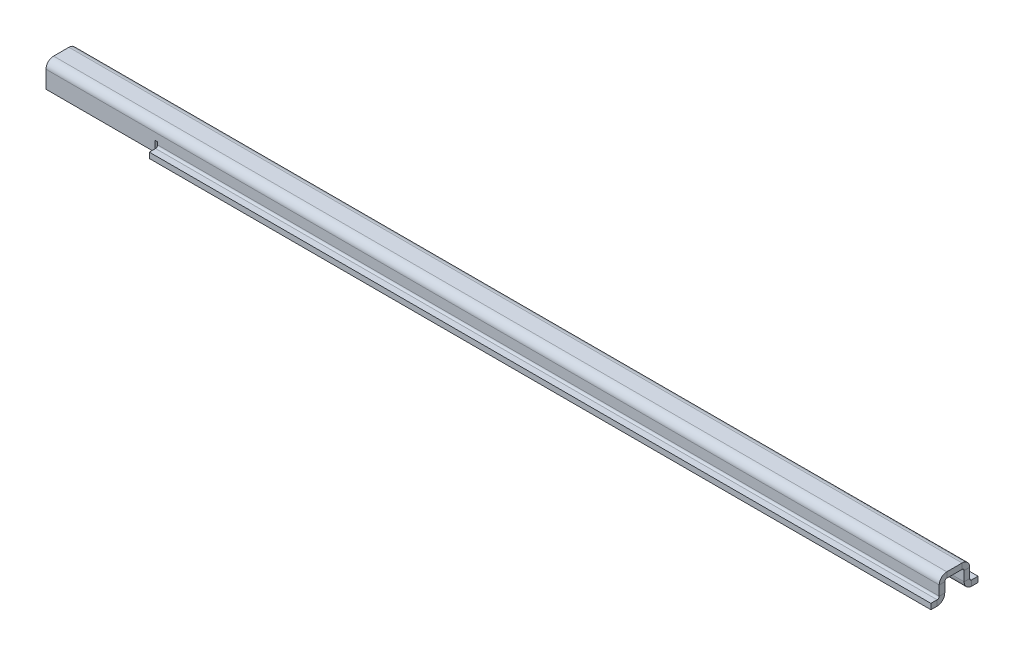
SolidWorks part; units mm, degrees
note: The reader was unsure of these and kept them because the rebuilt part matched: flange length of "Edge-Flange1", "Edge-Flange3".
material "ASTM A36 Steel"
ref_plane "Front Plane" through (0, 0, 0) normal (0, 0, 1) x (1, 0, 0)
ref_plane "Top Plane" through (0, 0, 0) normal (0, 1, 0) x (1, 0, 0)
ref_plane "Right Plane" through (0, 0, 0) normal (1, 0, 0) x (0, 0, -1)
sketch "Sketch2" plane through (0, 0, 0) normal (0, 1, 0) x (1, 0, 0)
  line L1 (-161.2, 5.5) -> (161.2, 5.5)
  line L2 (-161.2, 5.5) -> (-161.2, -5.5)
  line L3 (-161.2, -5.5) -> (161.2, -5.5)
  line L4 (161.2, 5.5) -> (161.2, -5.5)
  line L5 (-161.2, 5.5) -> (161.2, -5.5) construction
  line L6 (-161.2, -5.5) -> (161.2, 5.5) construction
  point P0 (0, 0)
  dimension "D1" = 322.4
  dimension "D2" = 11
base flange "Base-Flange1" sketch "Sketch2" thickness 2 reverse thickness direction no parameters "D1"=0.7366
edge flange "Edge-Flange1" sketch "Sketch11" flange profiles "Sketch11", "Sketch12" flange angle 90 flange length 9 flange position material inside bend radius 0.7366 thickness 2 relief rectangular parameters "D6"=10, "D8"=1
sketch "Sketch11" plane through (0, -2, 5.5) normal (0, 0, 1) x (-1, 0, 0)
  line L0 (161.2, 0) -> (-161.2, 0) construction
  line L1 (161.2, 0) -> (-161.2, 0)
  line L2 (-161.2, 0) -> (-161.2, 7)
  line L3 (-161.2, 7) -> (161.2, 7)
  line L4 (161.2, 7) -> (161.2, 0)
sketch "Sketch12" plane through (0, -2, -5.5) normal (0, 0, -1) x (1, 0, 0)
  line L0 (161.2, 0) -> (-161.2, 0) construction
  line L1 (161.2, 0) -> (-161.2, 0)
  line L2 (-161.2, 0) -> (-161.2, 7)
  line L3 (-161.2, 7) -> (161.2, 7)
  line L4 (161.2, 7) -> (161.2, 0)
bend "EdgeBend1" bend radius 0.7366 bend angle 90 parameters "D5"=1
bend "EdgeBend2" bend radius 0.7366 bend angle 90 parameters "D5"=2
sketch "Sketch15" plane through (0, 0, -5.5) normal (0, 0, -1) x (-1, 0, 0)
  line L0 (-161.2, -9) -> (161.2, -9) construction
  line L1 (-140, -9) -> (-70, -9)
  line L2 (-140, -9) -> (-140, -15)
  line L3 (-140, -15) -> (-70, -15)
  line L4 (-70, -9) -> (-70, -15)
  line L5 (0, 46.1369) -> (0, -97.287) construction
  line L6 (-35, -9) -> (35, -9)
  line L7 (-35, -9) -> (-35, -15)
  line L8 (-35, -15) -> (35, -15)
  line L9 (35, -9) -> (35, -15)
  line L10 (70, -9) -> (140, -9)
  line L11 (70, -9) -> (70, -15)
  line L12 (70, -15) -> (140, -15)
  line L13 (140, -9) -> (140, -15)
  dimension "D1" = 70
  dimension "D2" = 35
  dimension "D3" = 35
  dimension "D4" = 6
edge flange "Edge-Flange3" sketch "Sketch31" flange profiles "Sketch31", "Sketch32" flange angle 90 flange length 5 flange position material inside bend radius 0.7366 thickness 2 relief rectangular parameters "D6"=10, "D8"=1
sketch "Sketch31" plane through (0, -9, 5.5) normal (0, -1, 0) x (1, 0, 0)
  line L0 (-161.2, 0) -> (-161.2, -2) construction
  line L2 (-120.9, 0) -> (-120.9, 3)
  line L3 (-120.9, 3) -> (161.2, 3)
  line L4 (161.2, 3) -> (161.2, 0)
  line L11 (-161.2, 0) -> (161.2, 0) construction
  line L12 (-120.9, 0) -> (161.2, 0)
  dimension "D1" = 40.3
sketch "Sketch32" plane through (0, -9, -5.5) normal (0, -1, 0) x (-1, 0, 0)
  line L0 (161.2, 0) -> (161.2, -2) construction
  line L2 (120.9, 0) -> (120.9, 3)
  line L3 (120.9, 3) -> (-161.2, 3)
  line L4 (-161.2, 3) -> (-161.2, 0)
  line L5 (-161.2, 0) -> (161.2, 0) construction
  line L6 (-161.2, 0) -> (120.9, 0)
  dimension "D1" = 40.3
bend "EdgeBend5" bend radius 0.7366 bend angle 90 parameters "D5"=3
bend "EdgeBend6" bend radius 0.7366 bend angle 90 parameters "D5"=4
sketch "Bend-Lines1" [suppressed] plane through (0, 0, 0) normal (0, 1, 0) x (1, 0, 0)
sketch "Bounding-Box1" [suppressed] plane through (0, 0, 0) normal (0, 1, 0) x (1, 0, 0)
sheet metal parameters "Sheet-Metal1" thickness 2 parameters "D1"=0.7366
flat pattern "Flat-Pattern1" [suppressed]
sketch "Bend-Lines2" plane through (0, 0, 0) normal (0, 1, 0) x (1, 0, 0)
sketch3d "Bounding-Box2" [suppressed]
  line L0 (-161.2, -5.5, 0) -> (161.2, -5.5, 0) construction
  line L1 (-161.2, 5.5, 0) -> (161.2, 5.5, 0) construction
  line L2 (-161.2, -5.5, 0) -> (-161.2, 5.5, 0) construction
  line L3 (161.2, -5.5, 0) -> (161.2, 5.5, 0) construction
sheet metal parameters "Sheet-Metal2" thickness 2 parameters "D1"=0.7366
flat pattern "Flat-Pattern1" [suppressed]
sketch "Bend-Lines2" plane through (0, 0, 0) normal (0, 1, 0) x (1, 0, 0)
  line L0 (161.2, 4.1273) -> (-161.2, 4.1273) construction
  line L1 (-161.2, -4.1273) -> (161.2, -4.1273) construction
  line L2 (161.2, 4.1273) -> (-161.2, 4.1273) construction
  line L3 (-161.2, -4.1273) -> (161.2, -4.1273) construction
sketch3d "Bounding-Box2" [suppressed]
  line L0 (161.2, -27.7546, 0) -> (-161.2, -27.7546, 0) construction
  line L1 (161.2, 27.7546, 0) -> (-161.2, 27.7546, 0) construction
  line L2 (161.2, -27.7546, 0) -> (161.2, 27.7546, 0) construction
  line L3 (-161.2, -27.7546, 0) -> (-161.2, 27.7546, 0) construction
bend of the flat pattern "Flatten-<EdgeBend1>1"
bend of the flat pattern "Flatten-<EdgeBend2>1"
sketch "Sketch15-1" plane through (0, 0, -2.7546) normal (0, 1, 0) x (-1, 0, 0)
  line L1 (-140, -25) -> (-70, -25)
  line L2 (-140, -25) -> (-140, -31)
  line L3 (-140, -31) -> (-70, -31)
  line L4 (-70, -25) -> (-70, -31)
  line L5 (0, 46.1369) -> (0, -97.287) construction
  line L6 (-35, -25) -> (35, -25)
  line L7 (-35, -25) -> (-35, -31)
  line L8 (-35, -31) -> (35, -31)
  line L9 (35, -25) -> (35, -31)
  line L10 (70, -25) -> (140, -25)
  line L11 (70, -25) -> (70, -31)
  line L12 (70, -31) -> (140, -31)
  line L13 (140, -25) -> (140, -31)
  dimension "D1" = 70
  dimension "D2" = 35
  dimension "D3" = 35
  dimension "D4" = 6
sheet metal parameters "Sheet-Metal6" thickness 2 parameters "D1"=0.7366
flat pattern "Flat-Pattern1" [suppressed]
sketch "Bend-Lines2" plane through (0, 0, 0) normal (0, 1, 0) x (1, 0, 0)
  line L0 (161.2, 4.1273) -> (-161.2, 4.1273) construction
  line L1 (-161.2, -4.1273) -> (161.2, -4.1273) construction
  line L2 (161.2, 4.1273) -> (-161.2, 4.1273) construction
  line L3 (-161.2, -4.1273) -> (161.2, -4.1273) construction
  line L4 (161.2, 10.382) -> (-120.9, 10.382) construction
  line L5 (-120.9, -10.382) -> (161.2, -10.382) construction
  line L6 (161.2, 10.382) -> (-120.9, 10.382) construction
  line L7 (-120.9, -10.382) -> (161.2, -10.382) construction
sketch3d "Bounding-Box2" [suppressed]
  line L0 (161.2, -14.0093, 0) -> (-161.2, -14.0093, 0) construction
  line L1 (161.2, 14.0093, 0) -> (-161.2, 14.0093, 0) construction
  line L2 (161.2, -14.0093, 0) -> (161.2, 14.0093, 0) construction
  line L3 (-161.2, -14.0093, 0) -> (-161.2, 14.0093, 0) construction
bend of the flat pattern "Flatten-<EdgeBend1>1"
bend of the flat pattern "Flatten-<EdgeBend2>1"
bend of the flat pattern "Flatten-<EdgeBend5>1"
bend of the flat pattern "Flatten-<EdgeBend6>1"
sketch "Sketch15-1" plane through (0, 0, -2.7546) normal (0, 1, 0) x (-1, 0, 0)
  line L1 (-140, -9) -> (-70, -9)
  line L2 (-140, -9) -> (-140, -15)
  line L3 (-140, -15) -> (-70, -15)
  line L4 (-70, -9) -> (-70, -15)
  line L5 (0, 46.1369) -> (0, -97.287) construction
  line L6 (-35, -9) -> (35, -9)
  line L7 (-35, -9) -> (-35, -15)
  line L8 (-35, -15) -> (35, -15)
  line L9 (35, -9) -> (35, -15)
  line L10 (70, -9) -> (140, -9)
  line L11 (70, -9) -> (70, -15)
  line L12 (70, -15) -> (140, -15)
  line L13 (140, -9) -> (140, -15)
  dimension "D1" = 70
  dimension "D2" = 35
  dimension "D3" = 35
  dimension "D4" = 6
